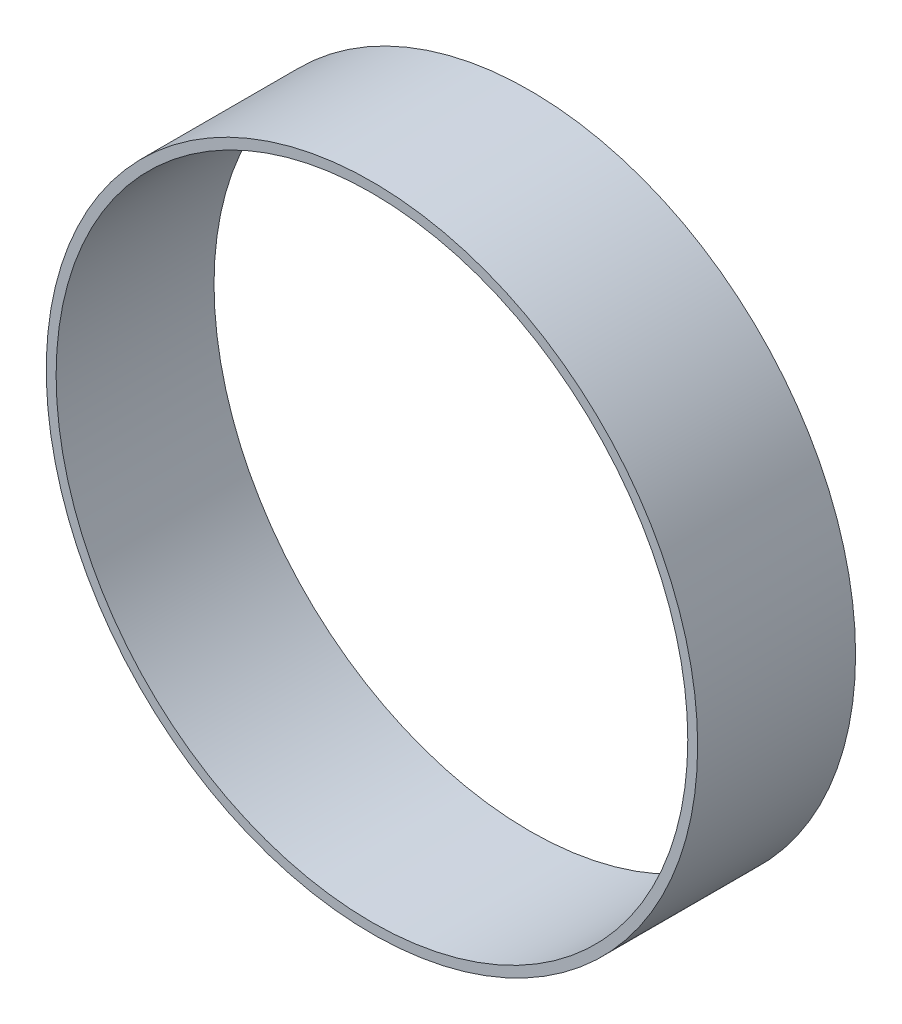
SolidWorks part; units mm, degrees
ref_plane "Front Plane" through (0, 0, 0) normal (1, 0, 0) x (0, 1, 0)
ref_plane "Top Plane" through (0, 0, 0) normal (0, 0, 1) x (0, 1, 0)
ref_plane "Right Plane" through (0, 0, 0) normal (0, 1, 0) x (-1, 0, 0)
sketch "Sketch1" plane through (0, 0, 0) normal (0, 0, 1) x (0, 1, 0)
  circle A0 centre (0, 0) radius 104.775
  circle A1 centre (0, 0) radius 101.6
  dimension "D1" = 209.55
  dimension "D2" = 3.175
extrude "Boss-Extrude1" add sketch "Sketch1" along normal blind 50.8
